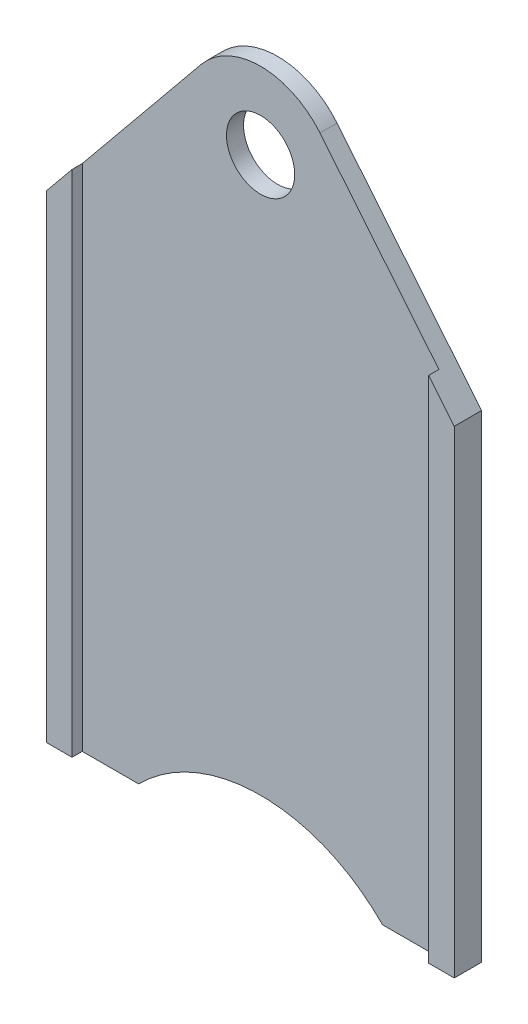
SolidWorks part; units mm, degrees
ref_plane "Plan de face" through (0, 0, 0) normal (0, 0, 1) x (1, 0, 0)
ref_plane "Plan de dessus" through (0, 0, 0) normal (0, 1, 0) x (1, 0, 0)
ref_plane "Plan de droite" through (0, 0, 0) normal (1, 0, 0) x (0, 0, -1)
sketch "Esquisse1" plane through (0, 0, 0) normal (0, 0, 1) x (1, 0, 0)
  line L0 (0, 0) -> (0, 70) construction
  line L1 (-23.9, 14) -> (-14.2829, 14)
  line L2 (-23.9, 14) -> (-23.9, 70)
  line L3 (-23.9, 70) -> (23.9, 70) construction
  line L4 (23.9, 14) -> (23.9, 70)
  line L5 (14.2829, 14) -> (23.9, 14)
  line L6 (6.9658, 90.6989) -> (23.9, 70)
  line L7 (-6.9658, 90.6989) -> (-23.9, 70)
  line L8 (0, 20) -> (-20.2661, 20) construction
  circle A0 centre (0, 0) radius 20 construction
  arc A1 (14.2829, 14) -> (-14.2829, 14) centre (0, 0) ccw
  circle A2 centre (0, 85) radius 4
  arc A3 (6.9658, 90.6989) -> (-6.9658, 90.6989) centre (0, 85) ccw
  dimension "D1" = 40
  dimension "D5" = 8
  dimension "D6" = 5
  dimension "D2" = 47.8
  dimension "D3" = 14
  dimension "D4" = 70
  dimension "D7" = 15
  dimension "D8" = 65
extrude "Boss.-Extru.1" add sketch "Esquisse1" along normal blind 2
sketch "Esquisse2" plane through (0, 0, 2) normal (0, 0, 1) x (1, 0, 0)
  line L0 (-6.9658, 90.6989) -> (-23.9, 70) construction
  line L1 (-23.9, 14) -> (-20.9, 14)
  line L2 (-23.9, 14) -> (-23.9, 70)
  line L4 (-20.9, 14) -> (-20.9, 73.6669)
  line L5 (23.9, 14) -> (20.9, 14)
  line L6 (23.9, 14) -> (23.9, 70)
  line L8 (20.9, 14) -> (20.9, 73.6669)
  line L9 (23.9, 70) -> (6.9658, 90.6989) construction
  line L10 (-20.9, 73.6669) -> (-23.9, 70)
  line L11 (23.9, 70) -> (20.9, 73.6669)
  dimension "D1" = 3
extrude "Boss.-Extru.2" add sketch "Esquisse2" along normal blind 1.2
ref_axis "Axe1" through (0, 85, 17.2118) along (0, 0, -1)
ref_plane "Plan Medien" through (0, 0, 1) normal (0, 0, 1) x (1, 0, 0)
